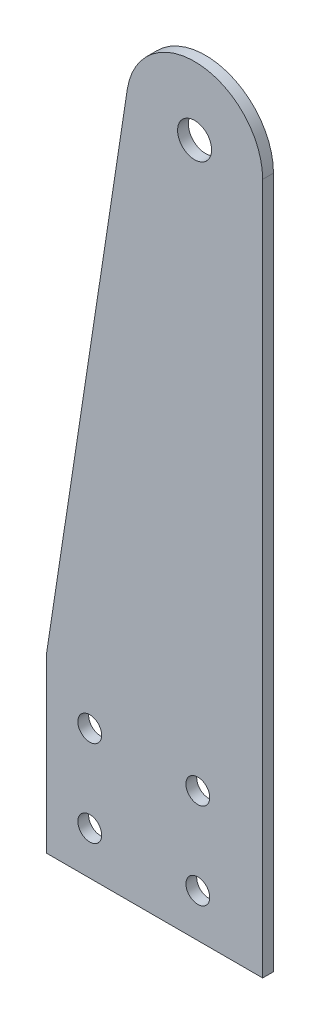
SolidWorks part; units mm, degrees
ref_plane "Front Plane" through (0, 0, 0) normal (0, 0, 1) x (1, 0, 0)
ref_plane "Top Plane" through (0, 0, 0) normal (0, 1, 0) x (1, 0, 0)
ref_plane "Right Plane" through (0, 0, 0) normal (1, 0, 0) x (0, 0, -1)
sketch "Sketch1" plane through (0, 0, 0) normal (0, 0, 1) x (1, 0, 0)
  line L0 (-31.75, -25.4) -> (31.75, -25.4)
  line L2 (31.75, -25.4) -> (31.75, 177.8)
  line L3 (-8.0209, 180.8186) -> (-31.75, 25.4)
  line L5 (-31.75, 25.4) -> (-31.75, -25.4)
  line L6 (-31.75, 25.4) -> (31.75, -25.4) construction
  line L13 (-19.05, -12.7) -> (12.7, -12.7) construction
  line L14 (-19.05, -12.7) -> (-19.05, 12.7) construction
  line L15 (-19.05, 12.7) -> (12.7, 12.7) construction
  line L16 (12.7, -12.7) -> (12.7, 12.7) construction
  line L17 (-19.05, -12.7) -> (12.7, 12.7) construction
  line L18 (-19.05, 12.7) -> (12.7, -12.7) construction
  arc A0 (-8.0209, 180.8186) -> (31.75, 177.8) centre (11.75, 177.8) cw
  circle A1 centre (11.75, 177.8) radius 5
  circle A6 centre (-19.05, 12.7) radius 3.5
  circle A7 centre (12.7, 12.7) radius 3.5
  circle A8 centre (12.7, -12.7) radius 3.5
  circle A9 centre (-19.05, -12.7) radius 3.5
  point P7 (0, 0)
  point P8 (0, 0)
  point P9 (-3.175, 0)
  dimension "D2" = 10
  dimension "D6" = 20
  dimension "D5" = 19.05
  dimension "D9" = 7
  dimension "D1" = 50.8
  dimension "D3" = 63.5
  dimension "D4" = 152.4
  dimension "D7" = 25.4
  dimension "D8" = 31.75
extrude "Boss-Extrude1" add sketch "Sketch1" along normal blind 3.175
